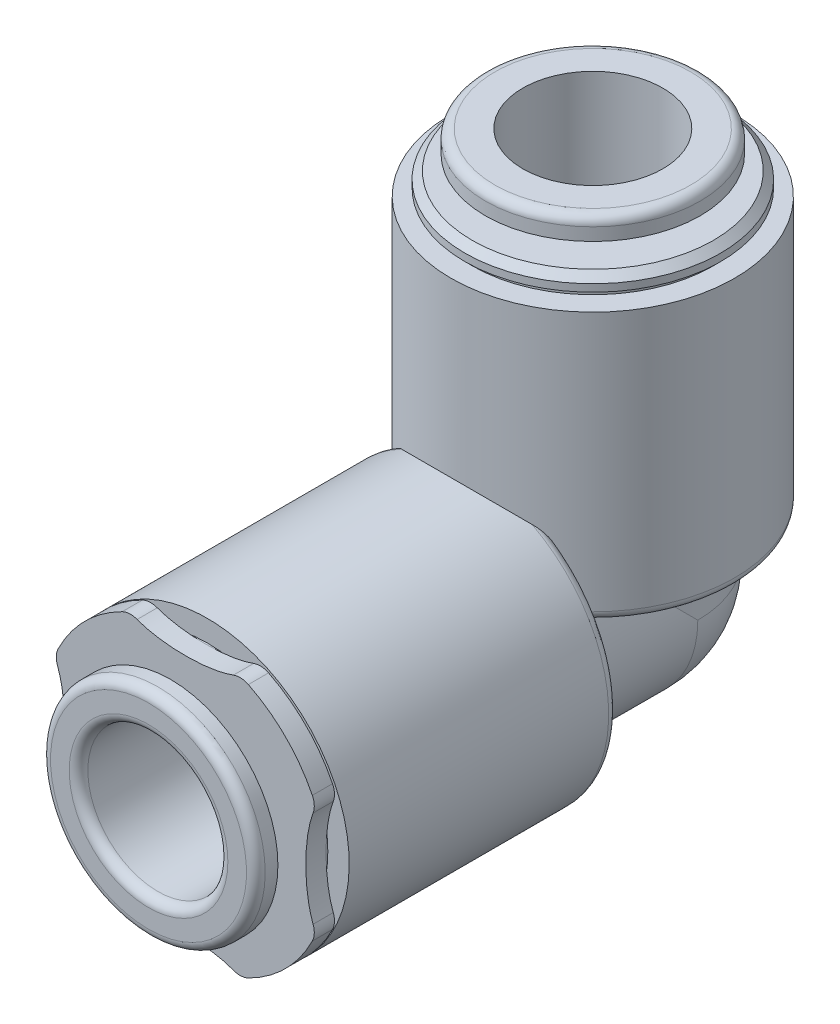
SolidWorks part; units mm, degrees
material "Delrin 2700 NC010, Low Viscosity Acetal Copolymer (SS)"
ref_plane "Front Plane" through (0, 0, 0) normal (0, 0, 1) x (1, 0, 0)
ref_plane "Top Plane" through (0, 0, 0) normal (0, 1, 0) x (1, 0, 0)
ref_plane "Right Plane" through (0, 0, 0) normal (1, 0, 0) x (0, 0, -1)
sketch "Sketch0" plane through (0, 0, 0) normal (1, 0, 0) x (0, 0, -1)
  line L0 (0, 0) -> (-30.226, 0) construction
  line L1 (0, 0) -> (0, 25.4) construction
  line L2 (-30.226, 4.7625) -> (-30.226, -4.7625) construction
  line L3 (-30.226, 9.652) -> (-30.226, -9.652) construction
  line L4 (-10.414, -3.81) -> (-10.414, 3.81) construction
  line L5 (-4.7625, 25.4) -> (4.7625, 25.4) construction
  line L6 (-3.81, 5.588) -> (3.81, 5.588) construction
  line L7 (-9.652, 25.4) -> (9.652, 25.4) construction
  point P10 (-10.414, 0)
  point P15 (0, 5.588)
  dimension "A" = 39.878
  dimension "SS Tube OD" = 9.525
  dimension "B" = 30.226
  dimension "E" = 7.62
  dimension "SS Depth" = 19.812
  dimension "Plastic Tube OD" = 9.525
  dimension "Plastic Depth" = 19.812
  dimension "D" = 35.052
  dimension "C" = 25.4
sketch "Sketch1" plane through (0, 0, 0) normal (1, 0, 0) x (0, 0, -1)
  line L0 (-30.226, 0) -> (7.1437, 0)
  line L2 (0, 7.1437) -> (-7.3025, 7.1437)
  line L3 (-7.9375, 7.7787) -> (-7.9375, 9.017)
  line L4 (-26.226, 9.652) -> (-26.226, 8.1995)
  line L5 (-26.726, 8.1995) -> (-26.226, 8.1995)
  line L6 (-8.5725, 9.652) -> (-26.226, 9.652)
  line L7 (-26.726, 8.1995) -> (-26.726, 8.6995)
  line L8 (-26.726, 8.6995) -> (-27.226, 8.6995)
  line L9 (-27.726, 8.1995) -> (-27.726, 5.3975)
  line L10 (-27.726, 5.3975) -> (-28.726, 5.3975)
  line L11 (-28.726, 5.3975) -> (-28.726, 7.3025)
  line L12 (-28.726, 7.3025) -> (-29.591, 7.3025)
  line L13 (-30.226, 6.6675) -> (-30.226, 0)
  line L16 (17.4957, 0) -> (22.4566, 0) construction
  line L17 (-30.226, 4.7625) -> (-10.414, 4.7625) construction
  line L18 (-10.414, 4.7625) -> (-10.414, 3.81) construction
  line L19 (-27.226, 8.6995) -> (-27.726, 8.1995)
  line L20 (-27.726, 8.1995) -> (-27.726, 8.6995) construction
  line L21 (-27.726, 8.6995) -> (-27.226, 8.6995) construction
  arc A0 (-7.3025, 7.1437) -> (-7.9375, 7.7787) centre (-7.3025, 7.7787) cw
  arc A1 (-7.9375, 9.017) -> (-8.5725, 9.652) centre (-8.5725, 9.017) ccw
  arc A2 (-29.591, 7.3025) -> (-30.226, 6.6675) centre (-29.591, 6.6675) ccw
  arc A3 (7.1437, 0) -> (0, 7.1437) centre (0, 0) ccw
  dimension "D7" = 0.635
  dimension "D8" = 0.635
  dimension "D3" = 14.2875
  dimension "L1" = 22.2885
  dimension "D4" = 9.525
  dimension "D5" = 14.605
  dimension "D6" = 10.795
  dimension "D9" = 1.5
  dimension "D10" = 1
  dimension "D12" = 0.5
  dimension "L" = 19.812
  dimension "D1" = 19.304
  dimension "D2" = 17.399
revolve "Revolve1" add sketch "Sketch1" angle 360 about L0
sketch "Sketch5" plane through (0, 0, 0) normal (1, 0, 0) x (0, 0, -1)
  line L0 (0, -7.1437) -> (0, 25.4)
  line L1 (0, 25.4) -> (6.6675, 25.4)
  line L2 (7.3025, 24.765) -> (7.3025, 23.9)
  line L3 (7.3025, 23.9) -> (5.3975, 23.9)
  line L4 (5.3975, 23.9) -> (5.3975, 22.9)
  line L5 (5.3975, 22.9) -> (8.1995, 22.9)
  line L6 (8.1995, 22.9) -> (8.6995, 22.9) construction
  line L7 (8.6995, 22.9) -> (8.6995, 22.4) construction
  line L8 (8.6995, 22.4) -> (8.1995, 22.9)
  line L9 (8.6995, 22.4) -> (8.6995, 21.9)
  line L10 (8.6995, 21.9) -> (8.1995, 21.9)
  line L11 (8.1995, 21.9) -> (8.1995, 21.4)
  line L12 (8.1995, 21.4) -> (9.652, 21.4)
  line L13 (9.652, 21.4) -> (9.652, 3.7465)
  line L14 (9.017, 3.1115) -> (7.7787, 3.1115)
  line L15 (7.1437, 2.4765) -> (7.1437, 0)
  line L16 (-9.652, 25.4) -> (9.652, 25.4) construction
  line L17 (4.7625, 25.4) -> (4.7625, 5.588) construction
  line L18 (4.7625, 5.588) -> (3.81, 5.588) construction
  line L19 (0, 0) -> (0, -17.8969) construction
  arc A0 (6.6675, 25.4) -> (7.3025, 24.765) centre (6.6675, 24.765) cw
  arc A1 (7.1437, 0) -> (0, -7.1437) centre (0, 0) cw
  arc A2 (7.7787, 3.1115) -> (7.1437, 2.4765) centre (7.7787, 2.4765) ccw
  arc A3 (9.652, 3.7465) -> (9.017, 3.1115) centre (9.017, 3.7465) cw
  dimension "D1" = 19.304
  dimension "R1" = 0.635
  dimension "R2" = 0.635
  dimension "D2" = 9.525
  dimension "D3" = 10.795
  dimension "D4" = 14.605
  dimension "D5" = 17.399
  dimension "D6" = 1.5
  dimension "D7" = 1
  dimension "D8" = 0.5
  dimension "L1" = 19.812
  dimension "D9" = 22.2885
revolve "Revolve2" add sketch "Sketch5" angle 360 about L19
sketch "Sketch2" plane through (0, 0, 0) normal (1, 0, 0) x (0, 0, -1)
  line L0 (-30.226, 4.7625) -> (-30.226, 0)
  line L1 (-30.226, 0) -> (3.81, 0)
  line L2 (-29.591, 4.7625) -> (-10.414, 4.7625)
  line L3 (-10.414, 4.7625) -> (-10.414, 3.81)
  line L4 (-10.414, 3.81) -> (0, 3.81)
  line L6 (-30.226, 4.7625) -> (-30.226, 5.3975)
  line L7 (-29.591, 4.7625) -> (-30.226, 4.7625) construction
  arc A0 (3.81, 0) -> (0, 3.81) centre (0, 0) ccw
  arc A1 (-30.226, 5.3975) -> (-29.591, 4.7625) centre (-29.591, 5.3975) ccw
  dimension "D1" = 0.635
revolve "Cut-Revolve1" cut sketch "Sketch2" angle 360 about L1
sketch "Sketch6" plane through (0, 0, 0) normal (1, 0, 0) x (0, 0, -1)
  line L0 (4.7625, 25.4) -> (0, 25.4)
  line L1 (0, 25.4) -> (0, -3.81)
  line L2 (0, -7.1437) -> (0, 0) construction
  line L3 (3.81, 5.588) -> (4.7625, 5.588)
  line L4 (4.7625, 5.588) -> (4.7625, 25.4)
  line L5 (3.81, 5.588) -> (3.81, 0)
  arc A0 (3.81, 0) -> (0, -3.81) centre (0, 0) cw
revolve "Cut-Revolve2" cut sketch "Sketch6" angle 360 about L1
sketch "Sketch3" plane through (0, 0, 27.726) normal (0, 0, 1) x (1, 0, 0)
  circle A0 centre (0, 0) radius 8.6995 construction
  circle A1 centre (0, 0) radius 9.652
  circle A2 centre (0, 0) radius 9.652 construction
  circle A3 centre (0, 0) radius 8.6995 construction
  circle A4 centre (0, 0) radius 8.1995 construction
  circle A5 centre (0, 0) radius 8.1995
extrude "Boss-Extrude1" add sketch "Sketch3" against normal offset from surface (1.373 mm away) 0.127 up to face at (0, -8.1995, 26.226)
sketch "Sketch4" plane through (0, 0, 27.726) normal (0, 0, 1) x (1, 0, 0)
  line L0 (0, 11.1045) -> (0, 9.652) construction
  line L1 (0, 9.652) -> (-1.4525, 9.652) construction
  line L2 (-1.4525, 9.652) -> (-2.905, 9.652) construction
  line L3 (-2.905, 9.652) -> (-4.3575, 9.652) construction
  circle A0 centre (0, 0) radius 9.652 construction
  circle A1 centre (0, 0) radius 9.652 construction
  circle A2 centre (0, 0) radius 8.1995 construction
  ellipse E0 centre (0, 9.652) end of major axis (4.3575, 9.652) minor radius 1.4525
extrude "Cut-Extrude1" cut sketch "Sketch4" against normal up to surface (1.373 mm away) up to face at (0, 9.652, 26.353)
fillet "Fillet1" radius 1.27 2 edges at (3.7311, 8.9017, 27.0395) (-3.7311, 8.9017, 27.0395)
pattern_circular "CirPattern1" count 4 over 360 about axis through (0, 0, -1.074) along (0, 0, 1) of "Cut-Extrude1", "Fillet1"
sketch "SketchX" plane through (0, 0, 0) normal (1, 0, 0) x (0, 0, -1)
  line L0 (-10.414, 4.7625) -> (-30.226, 4.7625)
  line L1 (-4.7625, 25.4) -> (-4.7625, 5.588)
  line L2 (-10.414, 4.7625) -> (-10.414, 3.81)
  line L3 (-10.414, -4.7625) -> (-30.226, -4.7625)
  line L4 (-10.414, -4.7625) -> (-10.414, -3.81)
  line L6 (-4.7625, 5.588) -> (-3.81, 5.588)
  line L8 (-10.414, -3.81) -> (0, -3.81)
  line L10 (-10.414, 3.81) -> (-3.81, 3.81)
  line L12 (-3.81, 5.588) -> (-3.81, 3.81)
  line L13 (4.7625, 25.4) -> (4.7625, 5.588)
  line L14 (4.7625, 5.588) -> (3.81, 5.588)
  line L16 (3.81, 5.588) -> (3.81, 0)
  arc A0 (3.81, 0) -> (0, -3.81) centre (0, 0) cw
sketch "SketchY" plane through (0, 0, 0) normal (0, 0, 1) x (1, 0, 0)
  line L0 (-4.7625, 25.4) -> (-4.7625, 5.588)
  line L1 (-4.7625, 5.588) -> (-3.81, 5.588)
  line L2 (-3.81, 5.588) -> (-3.81, 0)
  line L3 (4.7625, 25.4) -> (4.7625, 5.588)
  line L4 (4.7625, 5.588) -> (3.81, 5.588)
  line L5 (3.81, 5.588) -> (3.81, 0)
equation "\"D3@Sketch1\" = \"D4@Sketch1\" * 1.5"
equation "\"L1@Sketch1\" = \"L@Sketch1\" * 1.125"
equation "\"D5@Sketch1\" = \"D4@Sketch1\" + 0.20"
equation "\"D6@Sketch1\" = \"D4@Sketch1\"  + 0.05"
equation "\"D2@Sketch1\" = \"D1@Sketch1\" - 0.075"
equation "\"D9@Sketch5\" = \"L1@Sketch5\" * 1.125"
equation "\"D4@Sketch5\" = \"D2@Sketch5\" + 0.20"
equation "\"D3@Sketch5\" = \"D2@Sketch5\" + 0.05"
equation "\"D5@Sketch5\" = \"D1@Sketch5\" - 0.075"
